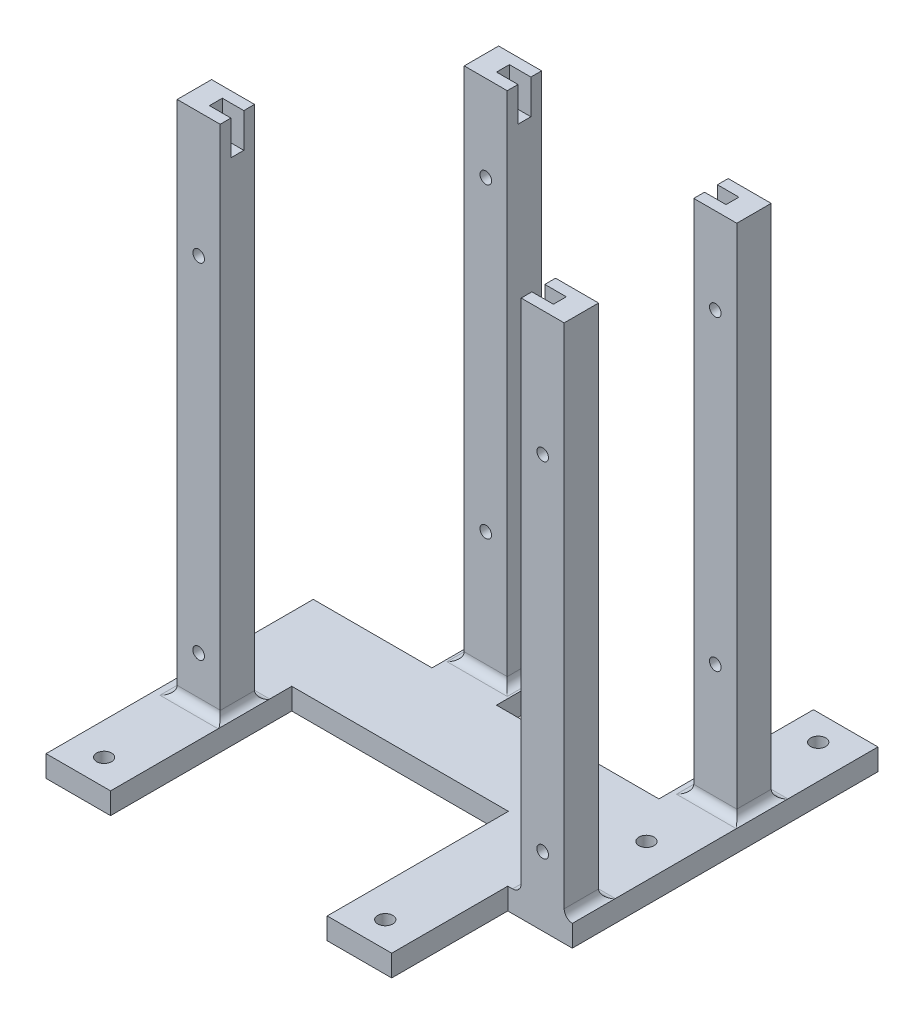
SolidWorks part; units mm, degrees
ref_plane "Front Plane" through (0, 0, 0) normal (0, 0, 1) x (1, 0, 0)
ref_plane "Top Plane" through (0, 0, 0) normal (0, 1, 0) x (1, 0, 0)
ref_plane "Right Plane" through (0, 0, 0) normal (1, 0, 0) x (0, 0, -1)
sketch "Sketch1" plane through (0, 0, 0) normal (0, 1, 0) x (1, 0, 0)
  line L3 (95.38, 27) -> (80.38, 27)
  line L4 (80.38, 27) -> (80.38, 0)
  line L5 (80.38, 0) -> (65.38, 0)
  line L6 (65.38, 0) -> (65.38, 42.14)
  line L7 (65.38, 42.14) -> (15, 42.14)
  line L8 (15, 42.14) -> (15, 0)
  line L9 (15, 0) -> (0, 0)
  line L11 (27.61, 82.14) -> (42.61, 82.14)
  line L12 (42.61, 82.14) -> (42.61, 62.14)
  line L13 (42.61, 62.14) -> (80.38, 62.14)
  line L14 (80.38, 62.14) -> (80.38, 98.08)
  line L15 (80.38, 98.08) -> (95.38, 98.08)
  line L16 (95.38, 98.08) -> (95.38, 27)
  line L17 (0, 0) -> (0, 62.14)
  line L18 (0, 62.14) -> (27.61, 62.14)
  line L19 (27.61, 62.14) -> (27.61, 82.14)
  circle A0 centre (7.5, 6) radius 1.75
  circle A1 centre (72.88, 6) radius 1.75
  circle A2 centre (87.49, 52.14) radius 1.75
  circle A3 centre (87.49, 92.08) radius 1.75
  point P17 (72.88, 0)
  point P18 (7.5, 0)
  point P25 (35.11, 82.14)
  dimension "D1" = 3.5
  dimension "D2" = 15
  dimension "D3" = 15
  dimension "D4" = 14.61
  dimension "D5" = 39.94
  dimension "D6" = 6
  dimension "D7" = 6
  dimension "D8" = 15
  dimension "D9" = 27
  dimension "D10" = 46.14
  dimension "D11" = 65.38
  dimension "D12" = 20
  dimension "D13" = 10
  dimension "D14" = 52.38
  dimension "D15" = 15
  dimension "D16" = 20
extrude "Boss-Extrude1" add sketch "Sketch1" along normal blind 5
sketch "Sketch2" plane through (0, 5, 0) normal (0, 1, 0) x (1, 0, 0)
  line L1 (93.49, 35) -> (83.49, 35)
  line L2 (93.49, 35) -> (93.49, 27)
  line L3 (93.49, 27) -> (83.49, 27)
  line L4 (83.49, 35) -> (83.49, 27)
  line L6 (13.49, 35) -> (3.49, 35)
  line L7 (13.49, 35) -> (13.49, 27)
  line L8 (13.49, 27) -> (3.49, 27)
  line L9 (3.49, 35) -> (3.49, 27)
  line L10 (80.38, 27) -> (95.38, 27) construction
  line L11 (95.38, 27) -> (95.38, 98.08) construction
  line L12 (42.61, 82.14) -> (27.61, 82.14) construction
  line L13 (30.11, 75.14) -> (40.11, 75.14)
  line L14 (30.11, 75.14) -> (30.11, 67.14)
  line L15 (30.11, 67.14) -> (40.11, 67.14)
  line L16 (40.11, 75.14) -> (40.11, 67.14)
  line L17 (83.49, 75.14) -> (93.49, 75.14)
  line L18 (83.49, 75.14) -> (83.49, 67.14)
  line L19 (83.49, 67.14) -> (93.49, 67.14)
  line L20 (93.49, 75.14) -> (93.49, 67.14)
  circle A0 centre (87.49, 52.14) radius 1.75 construction
  point P10 (8.49, 35)
  point P11 (88.49, 35)
  point P22 (35.11, 75.14)
  point P25 (35.11, 82.14)
  dimension "D5" = 15
  dimension "D1" = 80
  dimension "D2" = 10
  dimension "D3" = 8
  dimension "D4" = 1.89
extrude "Boss-Extrude2" add sketch "Sketch2" along normal blind 120
sketch "Sketch3" plane through (0, 0, -35) normal (0, 0, -1) x (-1, 0, 0)
  line L0 (-13.49, 125) -> (-3.49, 125) construction
  line L1 (-93.49, 125) -> (-83.49, 125) construction
  line L2 (-13.49, 5) -> (-3.49, 5) construction
  circle A0 centre (-8.49, 96) radius 2.5
  circle A1 centre (-8.49, 16) radius 2.5
  circle A2 centre (-88.49, 16) radius 2.5
  circle A3 centre (-88.49, 96) radius 2.5
  point P10 (-8.49, 125)
  point P13 (-88.49, 125)
  dimension "D1" = 5
  dimension "D2" = 11
  dimension "D3" = 80
extrude "Boss-Extrude3" add sketch "Sketch3" along normal blind 2
sketch "Sketch4" plane through (0, 0, -37) normal (0, 0, -1) x (-1, 0, 0)
  circle A0 centre (-8.49, 96) radius 1.35
  circle A1 centre (-8.49, 16) radius 1.35
  circle A2 centre (-88.49, 16) radius 1.35
  circle A3 centre (-88.49, 96) radius 1.35
  dimension "D1" = 2.7
extrude "Cut-Extrude1" cut sketch "Sketch4" against normal up to next
sketch "Sketch8" plane through (0, 0, -75.14) normal (0, 0, -1) x (-1, 0, 0)
  line L0 (-40.11, 125) -> (-30.11, 125) construction
  line L1 (-93.49, 125) -> (-83.49, 125) construction
  circle A0 centre (-35.11, 105) radius 2.5
  circle A1 centre (-35.11, 33.67) radius 2.5
  circle A2 centre (-88.49, 105) radius 2.5
  circle A3 centre (-88.49, 33.67) radius 2.5
  point P10 (-35.11, 125)
  point P13 (-88.49, 125)
  dimension "D1" = 5
  dimension "D2" = 20
  dimension "D3" = 71.33
extrude "Boss-Extrude5" add sketch "Sketch8" along normal blind 2
sketch "Sketch9" plane through (0, 0, -77.14) normal (0, 0, -1) x (-1, 0, 0)
  circle A0 centre (-35.11, 105) radius 1.35
  circle A1 centre (-35.11, 33.67) radius 1.35
  circle A2 centre (-88.49, 33.67) radius 1.35
  circle A3 centre (-88.49, 105) radius 1.35
  dimension "D1" = 2.7
extrude "Cut-Extrude3" cut sketch "Sketch9" against normal up to next
fillet "Fillet1" radius 2 15 edges at (93.49, 5, -31) (93.49, 5, -71.14) (88.49, 5, -67.14) (88.49, 5, -35) (83.49, 5, -31) (83.49, 5, -71.14) (88.49, 5, -75.14) (35.11, 5, -75.14) (30.11, 5, -71.14) (40.11, 5, -71.14) (35.11, 5, -67.14) (13.49, 5, -31) (8.49, 5, -27) (8.49, 5, -35) (3.49, 5, -31)
sketch "Sketch10" plane through (0, 125, 0) normal (0, 1, 0) x (1, 0, 0)
  line L0 (13.49, 27) -> (13.49, 35) construction
  line L1 (13.49, 32.5) -> (8.49, 32.5)
  line L2 (13.49, 32.5) -> (13.49, 29.5)
  line L3 (13.49, 29.5) -> (8.49, 29.5)
  line L4 (8.49, 32.5) -> (8.49, 29.5)
  line L5 (40.11, 67.14) -> (40.11, 75.14) construction
  line L6 (40.11, 72.64) -> (35.11, 72.64)
  line L7 (40.11, 72.64) -> (40.11, 69.64)
  line L8 (40.11, 69.64) -> (35.11, 69.64)
  line L9 (35.11, 72.64) -> (35.11, 69.64)
  line L10 (83.49, 75.14) -> (83.49, 67.14) construction
  line L11 (83.49, 72.64) -> (88.49, 72.64)
  line L12 (83.49, 72.64) -> (83.49, 69.64)
  line L13 (83.49, 69.64) -> (88.49, 69.64)
  line L14 (88.49, 72.64) -> (88.49, 69.64)
  line L15 (83.49, 35) -> (83.49, 27) construction
  line L16 (83.49, 32.5) -> (88.49, 32.5)
  line L17 (83.49, 32.5) -> (83.49, 29.5)
  line L18 (83.49, 29.5) -> (88.49, 29.5)
  line L19 (88.49, 32.5) -> (88.49, 29.5)
  line L20 (13.49, 35) -> (3.49, 35) construction
  line L21 (93.49, 35) -> (83.49, 35) construction
  point P24 (8.49, 31)
  point P27 (8.49, 35)
  point P28 (13.49, 31)
  point P29 (13.49, 31)
  point P30 (88.49, 31)
  point P33 (88.49, 35)
  point P34 (83.49, 71.14)
  point P35 (83.49, 71.14)
  dimension "D1" = 3
extrude "Cut-Extrude4" cut sketch "Sketch10" against normal blind 8
